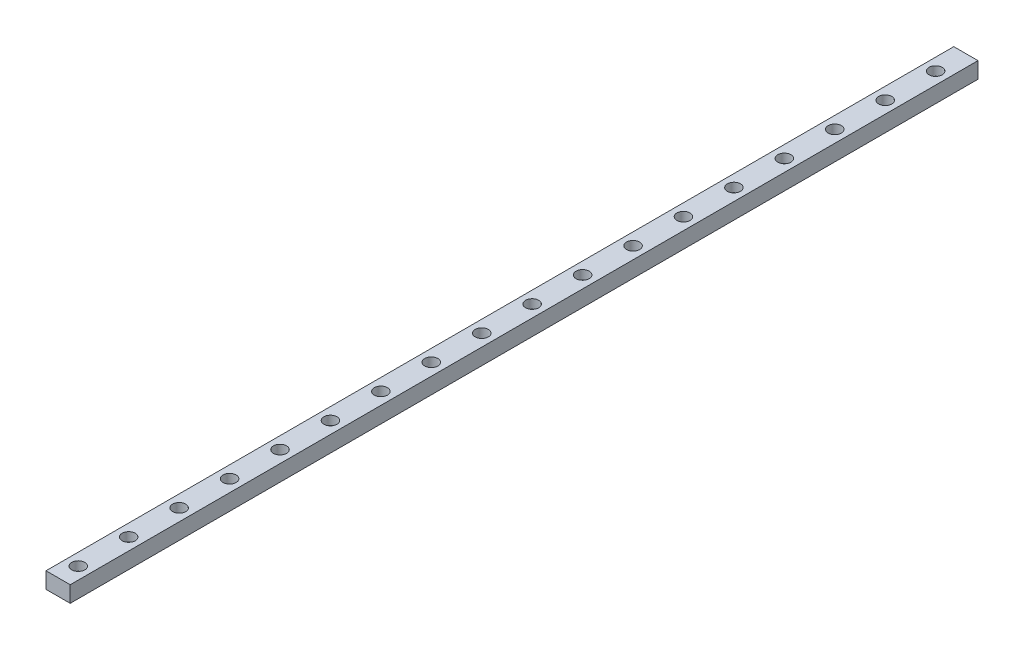
SolidWorks part; units mm, degrees
ref_plane "Front" through (0, 0, 0) normal (0, 0, 1) x (1, 0, 0)
ref_plane "Top" through (0, 0, 0) normal (0, 1, 0) x (1, 0, 0)
ref_plane "Right" through (0, 0, 0) normal (1, 0, 0) x (0, 0, -1)
sketch "Sketch1" plane through (0, 0, 0) normal (0, 0, 1) x (1, 0, 0)
  line L1 (0, 0) -> (12, 0)
  line L2 (0, 0) -> (0, 8)
  line L3 (0, 8) -> (12, 8)
  line L4 (12, 0) -> (12, 8)
  dimension "D1" = 12
  dimension "D2" = 8
extrude "Boss-Extrude1" add sketch "Sketch1" along normal blind 450
hole_wizard "CBORE for M3 SHCS1" positions "Sketch2" profile "Sketch3" counterbore size "M3" standard "ANSI Metric" end condition through all
sketch "Sketch2" plane through (0, 8, 0) normal (0, 1, 0) x (1, 0, 0)
  line L0 (12, -450) -> (0, -450) construction
  point P0 (6, -440)
  point P11 (6, -415)
  point P12 (6, -390)
  point P13 (6, -365)
  point P14 (6, -340)
  point P15 (6, -315)
  point P16 (6, -290)
  point P17 (6, -265)
  point P18 (6, -240)
  point P19 (6, -215)
  point P20 (6, -190)
  point P21 (6, -165)
  point P22 (6, -140)
  point P23 (6, -115)
  point P24 (6, -90)
  point P25 (6, -65)
  point P26 (6, -40)
  point P27 (6, -15)
  dimension "D1" = 10
  dimension "D2" = 18
sketch "Sketch3" plane through (6, 8, 440) normal (1, 0, 0) x (0, 0, 1)
  line L0 (0, 0) -> (0, 8)
  line L1 (0, 8) -> (1.7, 8)
  line L3 (1.7, 8) -> (1.7, 4.5)
  line L4 (1.7, 4.5) -> (3.25, 4.5)
  line L5 (3.25, 4.5) -> (3.25, 0)
  line L7 (3.25, 0) -> (0, 0)
  line L11 (0, -6.35) -> (0, 107.95) construction
  dimension "Thru Hole Dia." = 3.4
  dimension "Thru Hole Depth" = 8
  dimension "C'Bore Dia." = 6.5
  dimension "C'Bore Depth" = 4.5
equation "\"length\"=450"
equation "\"D1@Boss-Extrude1\"= \"length\""
